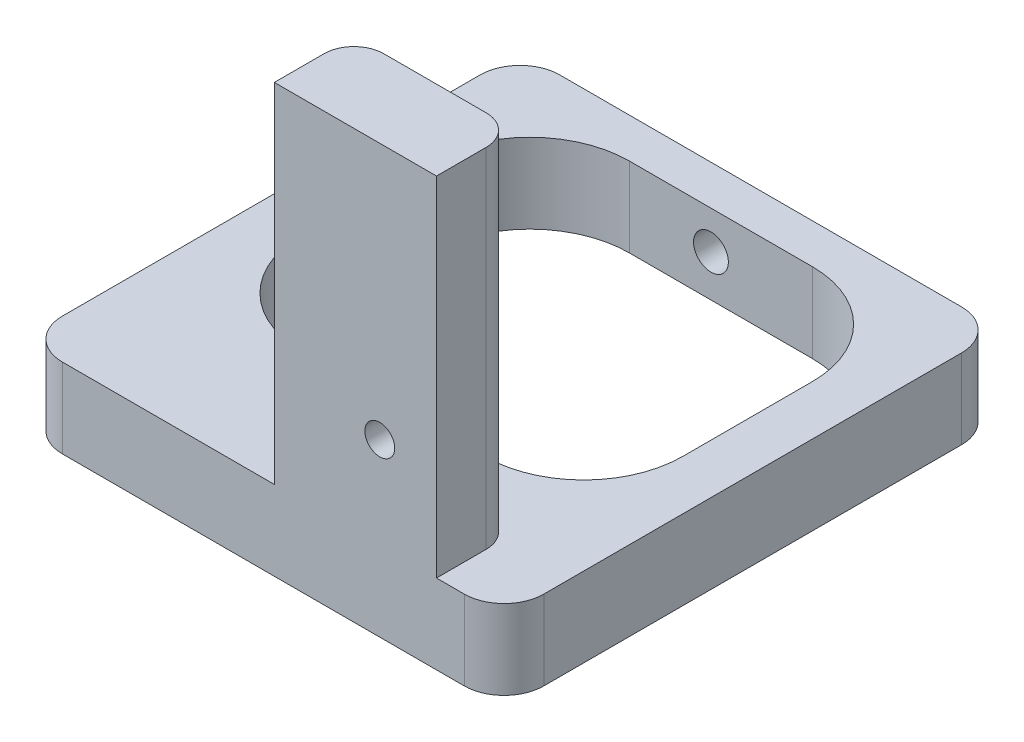
SolidWorks part; units mm, degrees
ref_plane "Front Plane" through (0, 0, 0) normal (0, 0, 1) x (1, 0, 0)
ref_plane "Top Plane" through (0, 0, 0) normal (0, 1, 0) x (1, 0, 0)
ref_plane "Right Plane" through (0, 0, 0) normal (1, 0, 0) x (0, 0, -1)
sketch "Sketch1" plane through (0, 0, 0) normal (0, 0, 1) x (1, 0, 0)
  line L1 (314.5907, 369.182) -> (330.8907, 369.182)
  line L2 (314.5907, 369.182) -> (314.5907, 334.182)
  line L3 (314.5907, 334.182) -> (330.8907, 334.182)
  line L4 (330.8907, 369.182) -> (330.8907, 334.182)
  line L5 (314.5907, 369.182) -> (330.8907, 334.182) construction
  line L6 (314.5907, 334.182) -> (330.8907, 369.182) construction
  circle A0 centre (325.1907, 343.382) radius 1.5
  point P4 (322.7407, 351.682)
  dimension "D3" = 3
  dimension "D4" = 5.7
  dimension "D1" = 16.3
  dimension "D2" = 35
  dimension "D5" = 25.8
extrude "Boss-Extrude1" add sketch "Sketch1" along normal blind 8
sketch "Sketch2" plane through (0, 334.182, 0) normal (0, -1, 0) x (-1, 0, 0)
  line L0 (-289.2818, -4) -> (-289.2818, -14) construction
  line L1 (-289.2818, 42) -> (-337.6818, 42)
  line L2 (-289.2818, 42) -> (-289.2818, -8)
  line L3 (-289.2818, -8) -> (-337.6818, -8)
  line L4 (-337.6818, 42) -> (-337.6818, -8)
  line L5 (-289.2818, 42) -> (-337.6818, -8) construction
  line L6 (-289.2818, -8) -> (-337.6818, 42) construction
  line L8 (-314.5907, -8) -> (-330.8907, -8) construction
  line L11 (-322.6818, 38) -> (-304.2818, 38)
  line L12 (-332.6818, 28) -> (-332.6818, 15)
  line L13 (-322.6818, 5) -> (-304.2818, 5)
  line L14 (-294.2818, 28) -> (-294.2818, 15)
  line L15 (-332.6818, 38) -> (-294.2818, 5) construction
  line L16 (-332.6818, 5) -> (-294.2818, 38) construction
  arc A0 (-304.2818, 38) -> (-294.2818, 28) centre (-304.2818, 28) cw
  arc A1 (-294.2818, 15) -> (-304.2818, 5) centre (-304.2818, 15) cw
  arc A2 (-332.6818, 15) -> (-322.6818, 5) centre (-322.6818, 15) ccw
  arc A3 (-332.6818, 28) -> (-322.6818, 38) centre (-322.6818, 28) cw
  point P0 (-313.4818, 17)
  point P9 (-313.4818, 21.5)
  dimension "D5" = 10
  dimension "D1" = 50
  dimension "D2" = 48.4
  dimension "D3" = 38.4
  dimension "D4" = 33
  dimension "D6" = 5
  dimension "D7" = 4
extrude "Boss-Extrude2" add sketch "Sketch2" along normal blind 8
sketch "Sketch3" plane through (0, 0, -42) normal (0, 0, -1) x (-1, 0, 0)
  line L0 (-289.2818, 326.182) -> (-289.2818, 334.182) construction
  circle A0 centre (-312.4818, 330.3624) radius 1.75
  dimension "D1" = 3.5
  dimension "D2" = 23.2
extrude "Cut-Extrude1" cut sketch "Sketch3" against normal up to surface (4 mm away) up to face at (313.4818, 330.182, -38)
sketch "Sketch4" plane through (289.2818, 0, 0) normal (-1, 0, 0) x (0, 0, 1)
  line L0 (-42, 326.182) -> (-42, 334.182) construction
  circle A0 centre (-21, 330.2021) radius 1.75
  dimension "D1" = 3.5
  dimension "D2" = 21
extrude "Cut-Extrude2" cut sketch "Sketch4" against normal up to surface (5 mm away) contours A0 up to face at (294.2818, 330.182, -21.5)
sketch "Sketch5" plane through (0, 0, 0) normal (0, 0, -1) x (-1, 0, 0)
  circle A0 centre (-325.1907, 343.382) radius 3
  dimension "D1" = 6
extrude "Cut-Extrude3" cut sketch "Sketch5" against normal blind 3.2
fillet "Fillet1" radius 4 4 edges at (337.6818, 330.182, -42) (289.2818, 330.182, -42) (337.6818, 330.182, 8) (289.2818, 330.182, 8)
fillet "Fillet2" radius 3 2 edges at (314.5907, 351.682, 0) (330.8907, 351.682, 0)
